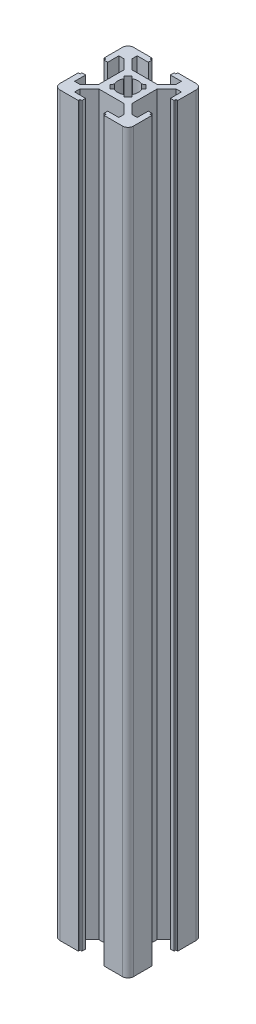
SolidWorks part; units mm, degrees
material "3.3547 (EN-AW 5083)"
ref_plane "Płaszczyzna przednia" through (0, 0, 0) normal (0, 0, 1) x (1, 0, 0)
ref_plane "Płaszczyzna górna" through (0, 0, 0) normal (0, 1, 0) x (1, 0, 0)
ref_plane "Płaszczyzna prawa" through (0, 0, 0) normal (1, 0, 0) x (0, 0, -1)
sketch "Szkic1" plane through (0, 0, 0) normal (0, 1, 0) x (1, 0, 0)
  line L0 (0, 10) -> (0, -10) construction
  line L1 (4.5, -4.5) -> (-4.5, -4.5)
  line L2 (4.5, -4.5) -> (4.5, 4.5)
  line L3 (4.5, 4.5) -> (-4.5, 4.5)
  line L4 (-4.5, -4.5) -> (-4.5, 4.5)
  line L5 (4.5, -4.5) -> (-4.5, 4.5) construction
  line L6 (4.5, 4.5) -> (-4.5, -4.5) construction
  line L7 (8.5, -10) -> (-8.5, -10)
  line L8 (10, -8.5) -> (10, 8.5)
  line L9 (8.5, 10) -> (-8.5, 10)
  line L10 (-10, -8.5) -> (-10, 8.5)
  line L11 (10, -10) -> (-10, 10) construction
  line L12 (10, 10) -> (-10, -10) construction
  line L13 (3.5, 10) -> (-3.5, 10)
  line L14 (-3.5, 10) -> (-3.5, 9.5)
  line L15 (-3.5, 9.5) -> (-3, 9.5)
  line L16 (-3, 9.5) -> (-3, 8.5)
  line L17 (-3, 8.5) -> (-6, 8.5)
  line L18 (-6, 8.5) -> (-6, 7.06)
  line L19 (-6, 7.06) -> (-3.4405, 4.5)
  line L20 (-1.9445, 3.0052) -> (-3.0052, 1.9445)
  line L21 (-1.9445, 3.0052) -> (-1.2713, 2.4385)
  line L22 (-3.0052, 1.9445) -> (-2.4385, 1.2713)
  line L23 (3.5, 10) -> (3.5, 9.5)
  line L24 (3.5, 9.5) -> (3, 9.5)
  line L25 (3, 9.5) -> (3, 8.5)
  line L26 (3, 8.5) -> (6, 8.5)
  line L27 (6, 8.5) -> (6, 7.06)
  line L28 (6, 7.06) -> (3.4405, 4.5)
  line L29 (1.9445, 3.0052) -> (3.0052, 1.9445)
  line L30 (1.9445, 3.0052) -> (1.2713, 2.4385)
  line L31 (3.0052, 1.9445) -> (2.4385, 1.2713)
  line L32 (1.9445, 3.0052) -> (1.2713, 2.4385)
  line L33 (3.0052, 1.9445) -> (1.9445, 3.0052)
  line L34 (3.0052, 1.9445) -> (2.4385, 1.2713)
  line L35 (7.06, 6) -> (4.5, 3.4405)
  line L36 (8.5, 6) -> (7.06, 6)
  line L37 (8.5, 3) -> (8.5, 6)
  line L38 (9.5, 3) -> (8.5, 3)
  line L39 (9.5, 3.5) -> (9.5, 3)
  line L40 (10, 3.5) -> (9.5, 3.5)
  line L41 (10, -3.5) -> (9.5, -3.5)
  line L42 (9.5, -3.5) -> (9.5, -3)
  line L43 (9.5, -3) -> (8.5, -3)
  line L44 (8.5, -3) -> (8.5, -6)
  line L45 (8.5, -6) -> (7.06, -6)
  line L46 (7.06, -6) -> (4.5, -3.4405)
  line L47 (3.0052, -1.9445) -> (2.4385, -1.2713)
  line L48 (3.0052, -1.9445) -> (1.9445, -3.0052)
  line L49 (1.9445, -3.0052) -> (1.2713, -2.4385)
  line L50 (3.0052, -1.9445) -> (2.4385, -1.2713)
  line L51 (1.9445, -3.0052) -> (3.0052, -1.9445)
  line L52 (1.9445, -3.0052) -> (1.2713, -2.4385)
  line L53 (6, -7.06) -> (3.4405, -4.5)
  line L54 (6, -8.5) -> (6, -7.06)
  line L55 (3, -8.5) -> (6, -8.5)
  line L56 (3, -9.5) -> (3, -8.5)
  line L57 (3.5, -9.5) -> (3, -9.5)
  line L58 (3.5, -10) -> (3.5, -9.5)
  line L59 (-3.5, -10) -> (-3.5, -9.5)
  line L60 (-3.5, -9.5) -> (-3, -9.5)
  line L61 (-3, -9.5) -> (-3, -8.5)
  line L62 (-3, -8.5) -> (-6, -8.5)
  line L63 (-6, -8.5) -> (-6, -7.06)
  line L64 (-6, -7.06) -> (-3.4405, -4.5)
  line L65 (-1.9445, -3.0052) -> (-1.2713, -2.4385)
  line L66 (-1.9445, -3.0052) -> (-3.0052, -1.9445)
  line L67 (-3.0052, -1.9445) -> (-2.4385, -1.2713)
  line L68 (-1.9445, -3.0052) -> (-1.2713, -2.4385)
  line L69 (-3.0052, -1.9445) -> (-1.9445, -3.0052)
  line L70 (-3.0052, -1.9445) -> (-2.4385, -1.2713)
  line L71 (-7.06, -6) -> (-4.5, -3.4405)
  line L72 (-8.5, -6) -> (-7.06, -6)
  line L73 (-8.5, -3) -> (-8.5, -6)
  line L74 (-9.5, -3) -> (-8.5, -3)
  line L75 (-9.5, -3.5) -> (-9.5, -3)
  line L76 (-10, -3.5) -> (-9.5, -3.5)
  line L77 (-10, 3.5) -> (-9.5, 3.5)
  line L78 (-9.5, 3.5) -> (-9.5, 3)
  line L79 (-9.5, 3) -> (-8.5, 3)
  line L80 (-8.5, 3) -> (-8.5, 6)
  line L81 (-8.5, 6) -> (-7.06, 6)
  line L82 (-7.06, 6) -> (-4.5, 3.4405)
  line L83 (-3.0052, 1.9445) -> (-2.4385, 1.2713)
  line L84 (-3.0052, 1.9445) -> (-1.9445, 3.0052)
  line L85 (-1.9445, 3.0052) -> (-1.2713, 2.4385)
  circle A0 centre (0, 0) radius 2.75
  arc A1 (10, -8.5) -> (8.5, -10) centre (8.5, -8.5) cw
  arc A2 (-10, -8.5) -> (-8.5, -10) centre (-8.5, -8.5) ccw
  arc A3 (10, 8.5) -> (8.5, 10) centre (8.5, 8.5) ccw
  arc A4 (-8.5, 10) -> (-10, 8.5) centre (-8.5, 8.5) ccw
  point P16 (0, 10)
  point P37 (-2.4749, 2.4749)
  dimension "D1" = 5.5
  dimension "D12" = 1.5
  dimension "D2" = 9
  dimension "D3" = 20
  dimension "D4" = 20
  dimension "D5" = 7
  dimension "D6" = 0.5
  dimension "D7" = 0.5
  dimension "D8" = 1
  dimension "D9" = 3
  dimension "D10" = 1.44
  dimension "D11" = 3.62
  dimension "D13" = 1.5
  dimension "D14" = 3.5
  dimension "D15" = 0.88
  dimension "D16" = 4
extrude "Dodanie-wyciągnięcie1" add sketch "Szkic1" along normal blind 807 contours L9 A4 L10 L77 L78 L79 L80 L81 L82 L4 L3 L19 L18 L17 L16 L15 L14 | L8 A3 L9 L23 L24 L25 L26 L27 L28 L3 L2 L35 L36 L37 L38 L39 L40 | L4 L1 L2 L3 A0 L47 L48 L49 L65 L66 L67 L22 L20 L21 L30 L29 L31 | L10 A2 L7 L59 L60 L61 L62 L63 L64 L1 L4 L71 L72 L73 L74 L75 L76 | A1 L8 L41 L42 L43 L44 L45 L46 L2 L1 L53 L54 L55 L56 L57 L58 L7 region at (7.2228, 0, 7.2228) region at (3.9703, 0, 4.3727) region at (-7.2228, 0, 7.2228) region at (7.2228, 0, -7.2228) region at (-7.2228, 0, -7.2228)
sketch "Skizze1" plane through (0, 0, 0) normal (0, 0, 1) x (1, 0, 0)
  line L0 (-83.4963, 200) -> (63.9108, 200)
  line L1 (63.9108, 200) -> (55.1488, 860.7548)
  line L2 (55.1488, 860.7548) -> (-83.4963, 858.9163)
  line L3 (-83.4963, 858.9163) -> (-83.4963, 200)
  dimension "D1" = 200
extrude "Schnitt-Linear austragen1" cut sketch "Skizze1" against normal mid plane 40
